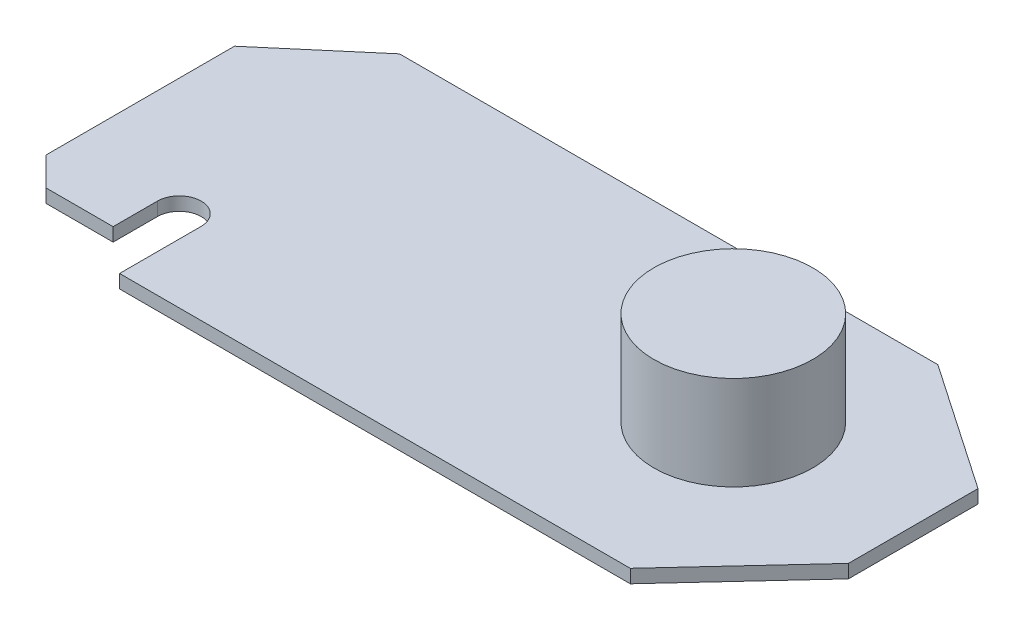
SolidWorks part; units mm, degrees
ref_plane "Front Plane" through (0, 0, 0) normal (0, 0, 1) x (1, 0, 0)
ref_plane "Top Plane" through (0, 0, 0) normal (0, 1, 0) x (1, 0, 0)
ref_plane "Right Plane" through (0, 0, 0) normal (1, 0, 0) x (0, 0, -1)
sketch "Sketch1" plane through (0, 0, 0) normal (0, 1, 0) x (1, 0, 0)
  line L0 (32.1929, 5.7315) -> (32.1929, -3.9185)
  line L1 (-24.0356, 6.5791) -> (-24.0356, -7.4609)
  line L2 (-17.3947, 12.2304) -> (22.7053, 12.2304)
  line L3 (-17.3947, 12.2304) -> (-24.0356, 6.5791)
  line L4 (22.7053, 12.2304) -> (32.1929, 5.7315)
  line L5 (-24.0356, -7.4609) -> (-21.9143, -9.5822)
  line L6 (-21.9143, -9.5822) -> (-16.9143, -9.5822)
  line L7 (-16.9143, -9.5822) -> (-16.9143, -6.2822)
  line L8 (-13.6543, -6.2822) -> (-13.6543, -12.3622)
  line L9 (-13.6543, -12.3622) -> (24.3857, -12.3622)
  line L10 (24.3857, -12.3622) -> (32.1929, -3.9185)
  arc A0 (-16.9143, -6.2822) -> (-13.6543, -6.2822) centre (-15.2843, -6.2822) cw
  dimension "D9" = 1.63
  dimension "D1" = 9.65
  dimension "D2" = 14.04
  dimension "D3" = 40.1
  dimension "D4" = 8.72
  dimension "D5" = 11.5
  dimension "D6" = 3
  dimension "D7" = 5
  dimension "D8" = 3.3
  dimension "D10" = 6.08
  dimension "D11" = 38.04
  dimension "D12" = 11.5
extrude "Boss-Extrude1" add sketch "Sketch1" along normal blind 1
sketch "Sketch2" plane through (0, 1, 0) normal (0, 1, 0) x (1, 0, 0)
  line L0 (32.1929, -3.9185) -> (32.1929, 5.7315) construction
  circle A0 centre (18.7929, 0.9065) radius 5.92
  point P5 (32.1929, 0.9065)
  dimension "D2" = 11.84
  dimension "D1" = 13.4
extrude "Boss-Extrude2" add sketch "Sketch2" along normal blind 7
sketch "Sketch3" plane through (0, 8, 0) normal (0, 1, 0) x (1, 0, 0)
  line L0 (32.1929, -3.9185) -> (32.1929, 5.7315) construction
  point P1 (18.7929, 0.9065)
ref_axis "Axis1" through (18.7929, 8, -0.9065) along (0, -1, 0)
ref_plane "Plane2" through (18.7929, 0, 0) normal (1, 0, 0) x (0, 0, -1)
